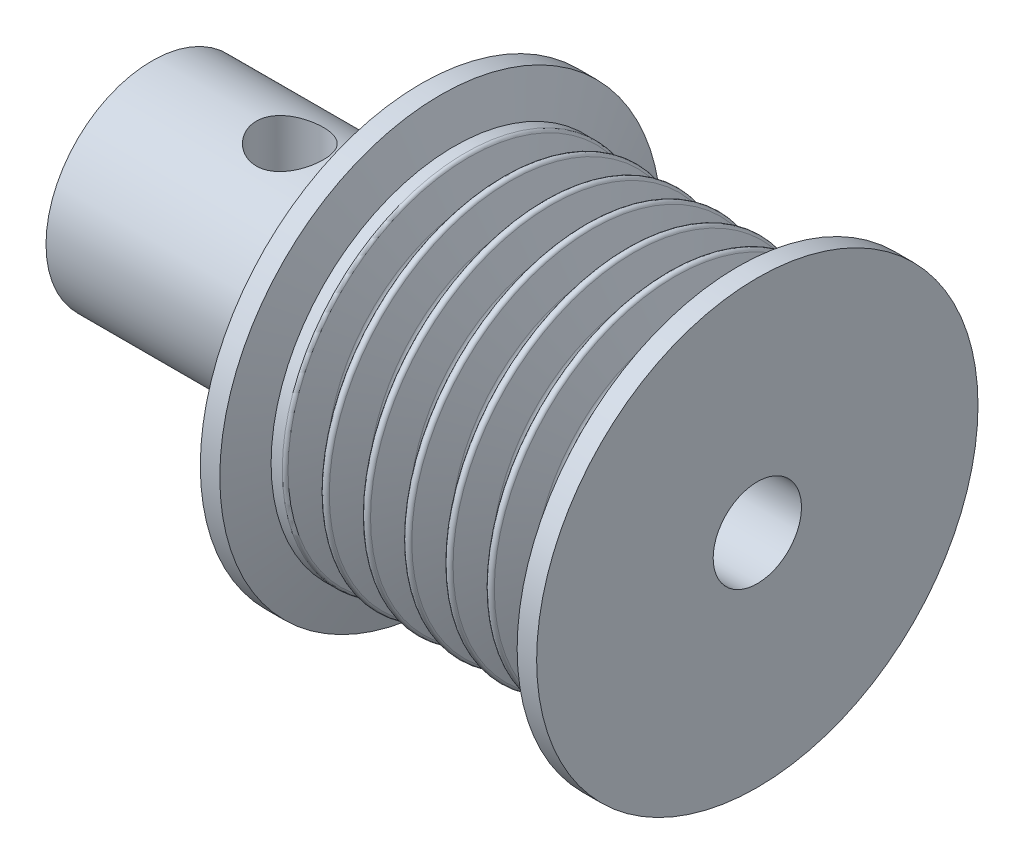
SolidWorks part; units mm, degrees
material "6061-T6 (SS)"
ref_plane "Front Plane" through (0, 0, 0) normal (0, 0, 1) x (1, 0, 0)
ref_plane "Top Plane" through (0, 0, 0) normal (0, 1, 0) x (1, 0, 0)
ref_plane "Right Plane" through (0, 0, 0) normal (1, 0, 0) x (0, 0, -1)
sketch "Sketch1" plane through (0, 0, 0) normal (0, 0, 1) x (1, 0, 0)
  line L0 (0, 0) -> (0, 2.5) construction
  line L1 (0, 2.5) -> (34.29, 2.5)
  line L2 (34.29, 2.5) -> (34.29, 12.5)
  line L3 (34.29, 12.5) -> (15.24, 12.5)
  line L4 (15.24, 12.5) -> (15.24, 6)
  line L5 (0, 0) -> (13.5959, 0) construction
  line L8 (15.24, 6) -> (0, 6)
  line L9 (0, 6) -> (0, 2.5)
  dimension "D1" = 25
  dimension "D2" = 5
  dimension "D3" = 19.05
  dimension "D6" = 12
  dimension "D7" = 15.24
revolve "Revolve1" add sketch "Sketch1" angle 360 about L5
sketch "Sketch2" plane through (0, 0, 0) normal (0, 0, 1) x (1, 0, 0)
  line L0 (29.4386, 12.5) -> (29.4386, 10.3699)
  line L1 (15.24, 6) -> (15.24, -6) construction
  line L2 (29.6295, 10.2362) -> (30.2251, 8.5999)
  line L3 (30.9889, 8.5999) -> (31.5845, 10.2362)
  line L4 (31.7754, 10.3699) -> (31.7754, 12.5)
  line L5 (31.7754, 12.5) -> (29.4386, 12.5)
  line L6 (29.4386, 11.43) -> (31.7754, 11.43) construction
  line L7 (15.24, 0) -> (34.29, 0) construction
  line L8 (29.6295, 10.2362) -> (31.5845, 10.2362) construction
  line L9 (29.4386, 12.5) -> (27.1018, 12.5) construction
  line L10 (34.29, 12.5) -> (15.24, 12.5) construction
  line L11 (27.1018, 12.5) -> (24.765, 12.5) construction
  line L13 (24.765, 0) -> (24.765, 12.5) construction
  line L15 (34.29, -12.5) -> (34.29, 12.5) construction
  arc A0 (29.4386, 10.3699) -> (29.6295, 10.2362) centre (29.4386, 10.1667) cw
  arc A1 (30.2251, 8.5999) -> (30.9889, 8.5999) centre (30.607, 8.7389) ccw
  arc A2 (31.5845, 10.2362) -> (31.7754, 10.3699) centre (31.7754, 10.1667) cw
  point P2 (15.24, 0)
  dimension "D1" = 0.4064
  dimension "D5" = 0.2032
  dimension "D2" = 2.3368
  dimension "D4" = 1.1938
  dimension "D6" = 40
  dimension "D7" = 11.43
revolve "Cut-Revolve1" cut sketch "Sketch2" angle 360 about L7
pattern_linear "LPattern1" count 6 spacing 2.3368 along (-1, 0, 0) of "Cut-Revolve1"
sketch "Sketch3" plane through (0, 0, 0) normal (0, 0, 1) x (1, 0, 0)
  line L0 (31.7754, 12.5) -> (33.1857, 12.5)
  line L1 (34.29, 12.5) -> (31.7754, 12.5) construction
  line L2 (33.1857, 12.5) -> (32.4104, 10.3699)
  line L3 (32.4104, 10.3699) -> (31.7754, 10.3699)
  line L4 (31.7754, 12.5) -> (31.7754, -12.5) construction
  line L5 (31.7754, 10.3699) -> (31.7754, 12.5)
  line L6 (31.7754, 10.3699) -> (31.7754, -10.3699) construction
  line L7 (30.607, 8.3325) -> (30.607, 11.4458) construction
  line L8 (24.765, 10.3699) -> (24.765, 14.7012) construction
  line L9 (17.7546, 10.3699) -> (17.7546, 12.5)
  line L10 (17.1196, 10.3699) -> (17.7546, 10.3699)
  line L11 (16.3443, 12.5) -> (17.1196, 10.3699)
  line L12 (17.7546, 12.5) -> (16.3443, 12.5)
  line L13 (0, 0) -> (26.9583, 0) construction
  arc A0 (30.2251, 8.5999) -> (30.9889, 8.5999) centre (30.607, 8.7389) ccw construction
  arc A1 (24.9559, 10.2362) -> (24.5741, 10.2362) centre (24.765, 10.1667) ccw construction
  dimension "D1" = 1.8034
  dimension "D2" = 20
revolve "Cut-Revolve2" cut sketch "Sketch3" angle 360 about L13
fillet "Fillet1" radius 0.762 1 edges at (15.24, 0, 6)
ref_plane "Plane1" through (0, 6, 0) normal (0, 1, 0) x (1, 0, 0)
sketch "Sketch6" plane through (0, 6, 0) normal (0, 1, 0) x (1, 0, 0)
  line L1 (7.811, 0) -> (0, 0) construction
  line L7 (11.24, 6) -> (11.24, -6) construction
  line L8 (14.478, 6) -> (0, 6) construction
  line L9 (0, -6) -> (14.478, -6) construction
  line L11 (15.24, 6.762) -> (15.24, -6.762) construction
  circle A0 centre (7.811, 0) radius 3.429 construction
  point P0 (7.811, 0)
  point P36 (7.8715, 0)
  point P37 (6.0494, 0)
  point P38 (7.2641, 0)
  point P39 (5.8469, 0)
  point P40 (0, 0)
  point P41 (6.0494, 0)
  point P42 (6.2518, 0)
  dimension "D1" = 6.858
  dimension "D2" = 4
hole_wizard "#10-24 Tapped Hole1" positions "Sketch6" profile "Sketch5" tap size "#10-24" standard "ANSI Inch" end condition up to next
sketch "Sketch5" plane through (7.811, 6, 0) normal (1, 0, 0) x (0, 0, 1)
  line L0 (0, 0) -> (0, 3.5)
  line L1 (0, 3.5) -> (1.8986, 3.5)
  line L2 (1.8986, 3.5) -> (1.8986, 0)
  line L5 (1.8986, 0) -> (0, 0)
  line L11 (0, -6.35) -> (0, 107.95) construction
  dimension "Thru Tap Drill Dia." = 3.7973
  dimension "Thru Tap Drill Depth" = 3.5
equation "\"D2@Sketch1\"=5mm"
equation "\"D4@Sketch2\"=0.094in/2"
equation "\"D1@Sketch1\"=25mm"
equation "\"D3@Sketch1\"=0.75in"
equation "\"D7@Sketch2\"=0.9in/2"
equation "\"D7@Sketch1\"=0.60in"
equation "\"D2@Sketch6\"=4mm"
equation "\"D6@Sketch1\"=12mm"
